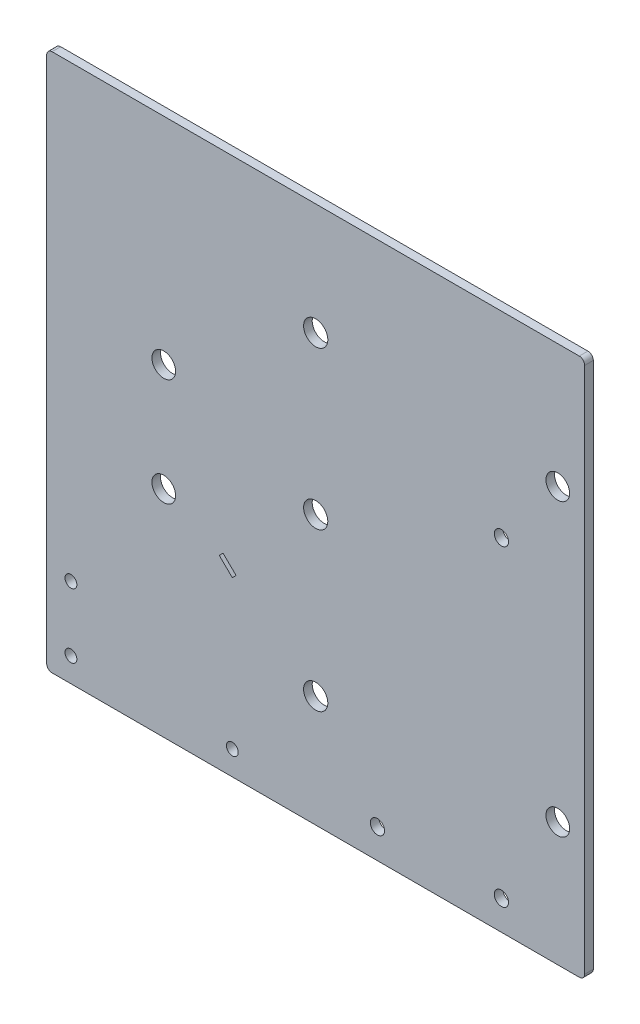
SolidWorks part; units mm, degrees
material "FR4_stuffedProtoboard"
ref_plane "Front Plane" through (0, 0, 0) normal (0, 0, 1) x (1, 0, 0)
ref_plane "Top Plane" through (0, 0, 0) normal (0, 1, 0) x (1, 0, 0)
ref_plane "Right Plane" through (0, 0, 0) normal (1, 0, 0) x (0, 0, -1)
sketch "Sketch1" plane through (0, 0, 0) normal (0, 0, 1) x (1, 0, 0)
  line L1 (-50, -50) -> (50, -50)
  line L2 (-50, -50) -> (-50, 50)
  line L3 (-50, 50) -> (50, 50)
  line L4 (50, -50) -> (50, 50)
  line L5 (-50, -50) -> (50, 50) construction
  line L6 (-50, 50) -> (50, -50) construction
  dimension "D1" = 100
extrude "Boss-Extrude1" add sketch "Sketch1" along normal blind 1.6
sketch "Sketch2" [suppressed] plane through (0, 0, 1.6) normal (0, 0, 1) x (1, 0, 0)
  circle A0 centre (0, 0) radius 50
  line M2 (50, -50) -> (50, 50)
  line M3 (50, 50) -> (-50, 50)
  line M4 (-50, 50) -> (-50, -50)
  line M5 (-50, -50) -> (50, -50)
  dimension "D1" = 100
extrude "Cut-Extrude1" [suppressed] cut sketch "Sketch2" against normal blind 1.6 contours A0 M3 M4 | A0 M4 M5 | A0 M5 M2 | A0 M2 M3
sketch "Sketch3" plane through (0, 0, 1.6) normal (0, 0, -1) x (-1, 0, 0)
  line L0 (-40, -22) -> (-50, -22) construction
  line L1 (-40, -32) -> (-40, -22) construction
  line L2 (-50, -32) -> (-40, -32) construction
  line L3 (-50, -22) -> (-50, -32) construction
  line L4 (-40, -22) -> (-50, -22)
  line L5 (-40, -32) -> (-40, -22)
  line L6 (-50, -32) -> (-40, -32)
  line L7 (-50, -22) -> (-50, -32)
  line L8 (-40, 22) -> (-40, 32) construction
  line L9 (-40, 32) -> (-50, 32) construction
  line L10 (-50, 32) -> (-50, 22) construction
  line L11 (-50, 22) -> (-40, 22) construction
  line L12 (-40, 22) -> (-40, 32)
  line L13 (-40, 32) -> (-50, 32)
  line L14 (-50, 32) -> (-50, 22)
  line L15 (-50, 22) -> (-40, 22)
  line L32 (17.2447, 25) -> (45.2447, 25) construction
  line L33 (45.2447, 25) -> (45.2447, -25) construction
  line L34 (17.2447, -25) -> (45.2447, -25) construction
  line L35 (17.2447, 25) -> (17.2447, -25) construction
  line L36 (17.2447, 25) -> (45.2447, 25)
  line L37 (45.2447, 25) -> (45.2447, -25)
  line L38 (17.2447, -25) -> (45.2447, -25)
  line L39 (17.2447, 25) -> (17.2447, -25)
  circle A3 centre (0, 0) radius 2.2479
  circle A4 centre (-34.525, -44.525) radius 1.325 construction
  circle A6 centre (-34.525, -44.525) radius 1.325
  circle A10 centre (0, -29.25) radius 2.25
  circle A11 centre (-45, -27) radius 2.2
  circle A12 centre (0, 29.25) radius 2.25
  circle A13 centre (-45, 27) radius 2.2
  circle A14 centre (-34.525, 13.525) radius 1.325 construction
  circle A15 centre (-34.525, 13.525) radius 1.325
  circle A16 centre (15.5, -45.5) radius 1.1 construction
  circle A17 centre (15.5, -45.5) radius 1.1
  circle A18 centre (45.5, -45.5) radius 1.1 construction
  circle A19 centre (45.5, -45.5) radius 1.1
  circle A20 centre (45.5, -33.5) radius 1.1 construction
  circle A21 centre (45.5, -33.5) radius 1.1
  circle A22 centre (-11.475, -44.525) radius 1.325 construction
  circle A23 centre (-11.475, -44.525) radius 1.325
  circle A24 centre (28.2447, -9.9994) radius 2.2 construction
  circle A25 centre (28.2447, -9.9994) radius 2.2
  circle A26 centre (28.2447, 10.0006) radius 2.2 construction
  circle A27 centre (28.2447, 10.0006) radius 2.2
  circle A28 centre (-45, 27) radius 2.2 construction
  circle A29 centre (-45, 27) radius 2.2
  circle A30 centre (-45, -27) radius 2.2 construction
  circle A31 centre (-45, -27) radius 2.2
  dimension "D1" = 4.4958
extrude "Cut-Extrude2" cut sketch "Sketch3" along normal through all contours A13 | A11 | A3 | A15 | A6 | A23 | A27 | A25 | A17 | A21 | A19 | A12 | A10 region at (0, 0, 1.6) region at (34.525, -44.525, 1.6) region at (45, -27, 1.6) region at (45, 27, 1.6) region at (34.525, 13.525, 1.6) region at (-15.5, -45.5, 1.6) region at (-45.5, -45.5, 1.6) region at (-45.5, -33.5, 1.6) region at (11.475, -44.525, 1.6) region at (-28.2447, -9.9994, 1.6) region at (-28.2447, 10.0006, 1.6)
sketch "Sketch4" plane through (0, 0, 1.6) normal (0, 0, 1) x (1, 0, 0)
  line L0 (38, -44.25) -> (38, -18.925) construction
  line L5 (38, -44.25) -> (38, -18.925)
  line L6 (11.75, -48) -> (34.25, -48) construction
  line L7 (11.75, -48) -> (34.25, -48)
  line L8 (8, -44.25) -> (8, 13.25) construction
  line L9 (8, -44.25) -> (8, 13.25)
  line L11 (33, -3) -> (33, -48) construction
  line L13 (34.25, 17) -> (11.75, 17)
  line L14 (38, 13.25) -> (38, -18.925)
  line L15 (-48, -48) -> (-13, -48) construction
  line L16 (-48, -48) -> (-13, -48)
  line L17 (-48, -31) -> (-48, -48) construction
  line L18 (-48, -31) -> (-48, -48)
  line L19 (-13, -40.5) -> (-13, -32.5) construction
  line L20 (-13, -40.5) -> (-13, -32.5)
  line L21 (-13, -48) -> (-13, -40.5) construction
  line L22 (-13, -48) -> (-13, -40.5)
  line L23 (-13, -32.5) -> (-13, -31) construction
  line L24 (-13, -32.5) -> (-13, -31)
  line L25 (-13, -31) -> (-48, -31) construction
  line L26 (-13, -31) -> (-48, -31)
  line L27 (-20, -34) -> (-20, -48) construction
  arc A0 (34.25, -48) -> (38, -44.25) centre (34.25, -44.25) ccw construction
  arc A1 (34.25, -48) -> (38, -44.25) centre (34.25, -44.25) ccw
  arc A2 (8, -44.25) -> (11.75, -48) centre (11.75, -44.25) ccw construction
  arc A3 (8, -44.25) -> (11.75, -48) centre (11.75, -44.25) ccw
  arc A4 (11.75, 17) -> (8, 13.25) centre (11.75, 13.25) ccw construction
  arc A5 (11.75, 17) -> (8, 13.25) centre (11.75, 13.25) ccw
  arc A6 (38, 13.25) -> (34.25, 17) centre (34.25, 13.25) ccw construction
  arc A7 (38, 13.25) -> (34.25, 17) centre (34.25, 13.25) ccw
  text T0 "Raspberry Pi Zero W" font "Century Gothic" height 2
  text T1 "Atheros" font "Century Gothic" height 2
  dimension "D1" = 5
  dimension "D2" = 20
  dimension "D3" = 3
  dimension "D4" = 7
fillet "Fillet1" radius 1 4 edges at (-50, -50, 0.8) (-50, 50, 0.8) (50, -50, 0.8) (50, 50, 0.8)
sketch "Sketch5" plane through (0, 0, 0) normal (0, 0, -1) x (-1, 0, 0)
  line L0 (-10, -33.25) -> (-10, -21.6463) construction
  line L5 (10, -21.6463) -> (10, -33.25) construction
  line L6 (-10, -33.25) -> (-10, -21.6463)
  line L7 (10, -21.6463) -> (10, -33.25)
  line L8 (-10, 21.6463) -> (-10, 33.25) construction
  line L9 (8, -35.25) -> (-8, -35.25) construction
  line L10 (-10, 21.6463) -> (-10, 33.25)
  line L11 (8, -35.25) -> (-8, -35.25)
  line L12 (-8, 35.25) -> (8, 35.25) construction
  line L13 (10, 33.25) -> (10, 21.6463) construction
  line L14 (-8, 35.25) -> (8, 35.25)
  line L15 (10, 33.25) -> (10, 21.6463)
  line L16 (14.7958, -17.2148) -> (17.2267, -14.8297)
  line L17 (17.2267, -14.8297) -> (17.9271, -15.5435)
  line L18 (17.9271, -15.5435) -> (15.4962, -17.9286)
  line L19 (15.4962, -17.9286) -> (14.7958, -17.2148)
  line L20 (16.7116, -16.7361) -> (13.0646, -13.0191) construction
  line L21 (10, -21.6446) -> (10, -33.2483)
  line L22 (8, -35.2483) -> (-8, -35.2483)
  line L23 (-10, -33.2483) -> (-10, -21.6446)
  line L24 (-10, 21.648) -> (-10, 33.2517)
  line L25 (-8, 35.2517) -> (8, 35.2517)
  line L26 (10, 33.2517) -> (10, 21.648)
  arc A0 (-10, -21.6463) -> (-11.0303, -19.8971) centre (-12, -21.6463) ccw construction
  arc A1 (11.0303, -19.8971) -> (10, -21.6463) centre (12, -21.6463) ccw construction
  arc A2 (18.4057, -13.3713) -> (11.0303, 19.8971) centre (0, 0) ccw construction
  arc A3 (-11.0303, 19.8971) -> (-11.0303, -19.8971) centre (0, 0) ccw construction
  arc A4 (-10, -21.6463) -> (-11.0303, -19.8971) centre (-12, -21.6463) ccw
  arc A5 (11.0303, -19.8971) -> (10, -21.6463) centre (12, -21.6463) ccw
  arc A6 (18.4057, -13.3713) -> (11.0303, 19.8971) centre (0, 0) ccw
  arc A7 (-11.0303, 19.8971) -> (-11.0303, -19.8971) centre (0, 0) ccw
  arc A8 (-8, 35.25) -> (-10, 33.25) centre (-8, 33.25) ccw construction
  arc A9 (-11.0303, 19.8971) -> (-10, 21.6463) centre (-12, 21.6463) ccw construction
  arc A10 (-10, -33.25) -> (-8, -35.25) centre (-8, -33.25) ccw construction
  arc A11 (-8, 35.25) -> (-10, 33.25) centre (-8, 33.25) ccw
  arc A12 (-11.0303, 19.8971) -> (-10, 21.6463) centre (-12, 21.6463) ccw
  arc A13 (-10, -33.25) -> (-8, -35.25) centre (-8, -33.25) ccw
  arc A14 (8, -35.25) -> (10, -33.25) centre (8, -33.25) ccw construction
  arc A15 (8, -35.25) -> (10, -33.25) centre (8, -33.25) ccw
  arc A16 (10, 33.25) -> (8, 35.25) centre (8, 33.25) ccw construction
  arc A17 (10, 21.6463) -> (11.0303, 19.8971) centre (12, 21.6463) ccw construction
  arc A18 (10, 33.25) -> (8, 35.25) centre (8, 33.25) ccw
  arc A19 (10, 21.6463) -> (11.0303, 19.8971) centre (12, 21.6463) ccw
  arc A20 (11.0303, -19.8954) -> (10, -21.6446) centre (12, -21.6446) ccw
  arc A21 (8, -35.2483) -> (10, -33.2483) centre (8, -33.2483) ccw
  arc A22 (-10, -33.2483) -> (-8, -35.2483) centre (-8, -33.2483) ccw
  arc A23 (-10, -21.6446) -> (-11.0303, -19.8954) centre (-12, -21.6446) ccw
  arc A24 (-11.0303, 19.8988) -> (-11.0303, -19.8954) centre (0, 0.0017) ccw
  arc A25 (-11.0303, 19.8988) -> (-10, 21.648) centre (-12, 21.648) ccw
  arc A26 (-8, 35.2517) -> (-10, 33.2517) centre (-8, 33.2517) ccw
  arc A27 (10, 33.2517) -> (8, 35.2517) centre (8, 33.2517) ccw
  arc A28 (10, 21.648) -> (11.0303, 19.8988) centre (12, 21.648) ccw
  arc A29 (11.0303, -19.8954) -> (11.0303, 19.8988) centre (0, 0.0017) ccw
  spline S1 degree 3 poles (372.2196, 918.75) (-700.7012, -812.1195) (949.1946, 524.9019) (-970.1934, -163.8529) knots -40.309414 -40.309414 -40.309414 -40.309414 42.332657 42.332657 42.332657 42.332657 only from (15.4367, -15.4367) to (18.4059, -13.3713) construction
  spline S3 degree 3 poles (15.4367, -15.4367) (16.4808, -14.8306) (17.4743, -14.1392) (18.4059, -13.3713) knots 0 0 0 0 1 1 1 1
extrude "Cut-Extrude4" cut sketch "Sketch5" against normal through all contours L18 L19 L16 L17
